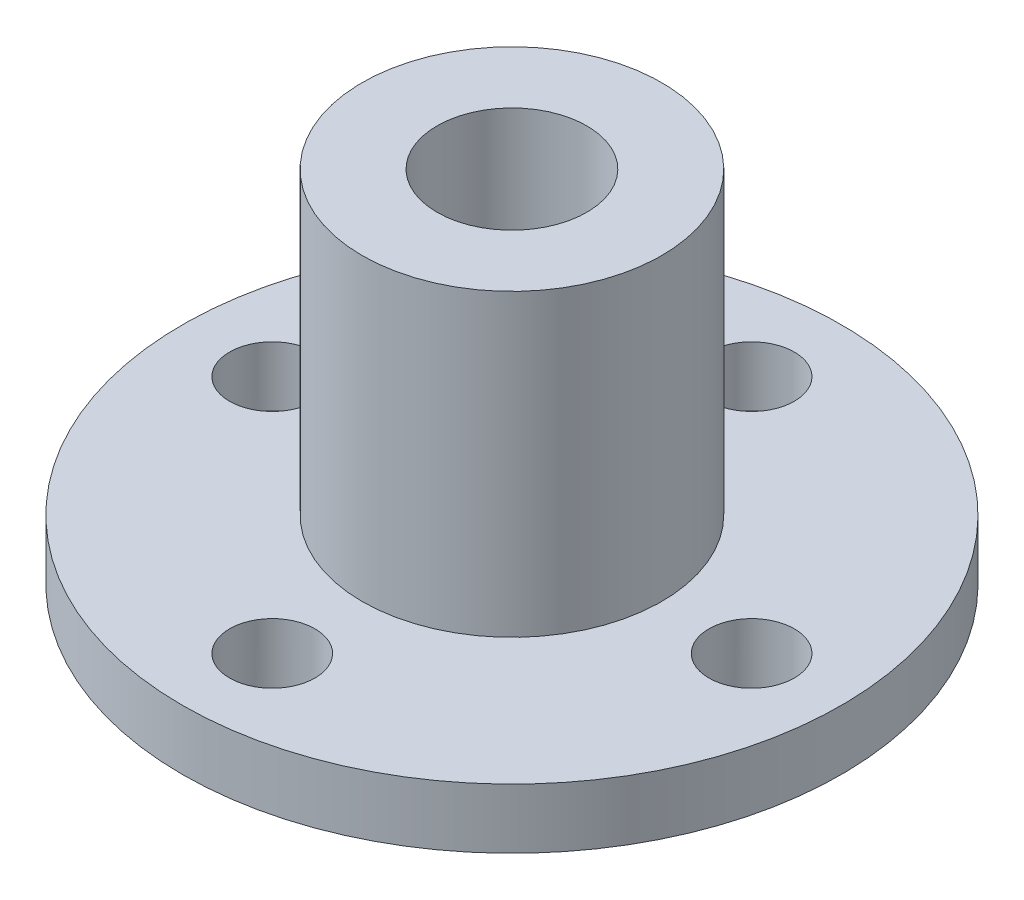
SolidWorks part; units mm, degrees
ref_plane "Front" through (0, 0, 0) normal (0, 0, 1) x (1, 0, 0)
ref_plane "Top" through (0, 0, 0) normal (0, 1, 0) x (1, 0, 0)
ref_plane "Right" through (0, 0, 0) normal (1, 0, 0) x (0, 0, -1)
sketch "Sketch1" plane through (0, 0, 0) normal (0, 1, 0) x (1, 0, 0)
  circle A0 centre (0, 0) radius 11
  circle A1 centre (0, 0) radius 5
  circle A2 centre (0, 0) radius 2.5
  dimension "D1" = 22
  dimension "D2" = 10
  dimension "D3" = 5
extrude "Boss-Extrude1" add sketch "Sketch1" along normal blind 2 contours A0 A1 | A1 A2 region at (-10.6889, 0, 0) region at (-4.8586, 0, 0)
extrude "Boss-Extrude2" add sketch "Sketch1<3>" along normal blind 12 contours A1 A2 region at (-4.8586, 0, 0)
sketch "Sketch1<3>" plane through (0, 0, 0) normal (0, 1, 0) x (1, 0, 0) same geometry as "Sketch1"
sketch "Sketch2" plane through (0, 2, 0) normal (0, 1, 0) x (1, 0, 0)
  line L0 (0, 5) -> (0, 8) construction
  line L1 (0, 8) -> (0, 11) construction
  circle A0 centre (0, 8) radius 1.425
  circle A1 centre (0, 0) radius 5 construction
  circle A2 centre (0, 0) radius 5 construction
  circle A3 centre (0, 0) radius 11 construction
  dimension "D1" = 2.85
extrude "Cut-Extrude1" cut sketch "Sketch2" against normal through all both and the other way through all
pattern_circular "CirPattern1" count 4 over 360 about axis through (0, 12, 0) along (0, -1, 0) of "Cut-Extrude1"
